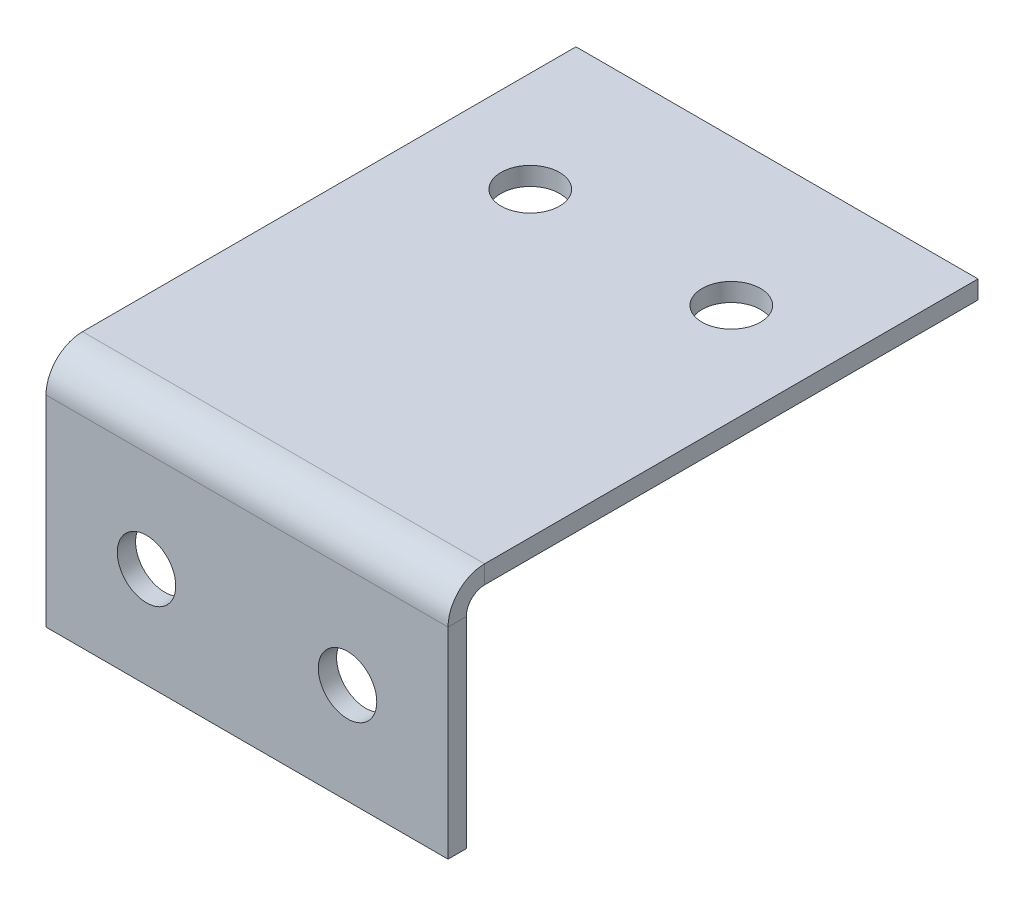
SolidWorks part; units mm, degrees
note: The reader was unsure of these and kept them because the rebuilt part matched: bend radius of "BaseBend1".
ref_plane "Front Plane" through (0, 0, 0) normal (0, 0, 1) x (1, 0, 0)
ref_plane "Top Plane" through (0, 0, 0) normal (0, 1, 0) x (1, 0, 0)
ref_plane "Right Plane" through (0, 0, 0) normal (1, 0, 0) x (0, 0, -1)
sketch "Sketch1" plane through (0, 0, 0) normal (1, 0, 0) x (0, 0, -1)
  line L0 (0, 0) -> (0, 19.05)
  line L1 (0, 19.05) -> (44.45, 19.05)
  dimension "D1" = 19.05
  dimension "D2" = 44.45
base flange "Base-Flange1" sketch "Sketch1" end condition mid plane depth 34.925 reverse direction yes thickness 1.5875 reverse thickness direction yes bend radius 1.5875
bend "BaseBend1" bend radius 1.5875 bend angle 90 parameters "D5"=1
sketch "Sketch6" plane through (0, 0, 1.5875) normal (0, 0, 1) x (1, 0, 0)
  line L0 (-17.4625, 8.7312) -> (17.4625, 8.7312) construction
  line L1 (-17.4625, 0) -> (-17.4625, 17.4625) construction
  line L2 (17.4625, 0) -> (17.4625, 17.4625) construction
  line L3 (-17.4625, 17.4625) -> (-8.7313, 8.7312) construction
  line L4 (-8.7313, 8.7312) -> (0, 17.4625) construction
  line L5 (-17.4625, 17.4625) -> (17.4625, 17.4625) construction
  line L6 (0, 17.4625) -> (8.7313, 8.7312) construction
  line L7 (8.7313, 8.7312) -> (17.4625, 17.4625) construction
  line L8 (-8.7313, 8.7312) -> (0, 0) construction
  line L9 (-17.4625, 0) -> (17.4625, 0) construction
  line L10 (0, 0) -> (8.7313, 8.7312) construction
  circle A0 centre (-8.7313, 8.7312) radius 2.54
  circle A1 centre (8.7313, 8.7312) radius 2.54
  dimension "D1" = 5.08
extrude "Cut-Extrude1" cut sketch "Sketch6" against normal blind 2.54
sketch "Sketch7" plane through (0, 20.6375, 0) normal (0, 1, 0) x (1, 0, 0)
  line L0 (-17.4625, 31.75) -> (17.4625, 31.75) construction
  line L4 (-17.4625, 1.5875) -> (-17.4625, 44.45) construction
  line L5 (17.4625, 1.5875) -> (17.4625, 44.45) construction
  line L6 (-17.4625, 44.45) -> (17.4625, 44.45) construction
  line L7 (-8.7313, 31.75) -> (0, 44.45) construction
  line L8 (0, 44.45) -> (8.7312, 31.75) construction
  line L9 (8.7312, 31.75) -> (17.4625, 44.45) construction
  circle A0 centre (-8.7313, 31.75) radius 2.54
  circle A1 centre (8.7312, 31.75) radius 2.54
  dimension "D2" = 12.7
  dimension "D1" = 5.08
extrude "Cut-Extrude2" cut sketch "Sketch7" against normal blind 2.54
sketch "Bend-Lines1" [suppressed] plane through (0, 0, 0) normal (0, 1, 0) x (1, 0, 0)
sketch "Bounding-Box1" [suppressed] plane through (0, 0, 0) normal (0, 1, 0) x (1, 0, 0)
sheet metal parameters "Sheet-Metal2" thickness 1.5875 parameters "D1"=1.5875
flat pattern "Flat-Pattern2" [suppressed]
sketch "Bend-Lines2" plane through (0, 26.9875, 0) normal (0, 1, 0) x (1, 0, 0)
  line L0 (18.2562, -0.2827) -> (-18.2562, -0.2827) construction
  line L1 (18.2562, -0.2827) -> (-18.2562, -0.2827) construction
sketch3d "Bounding-Box2" [suppressed]
  line L0 (0, -25.9655, 0) -> (0, 50.8, 0) construction
  line L1 (36.5125, -25.9655, 0) -> (36.5125, 50.8, 0) construction
  line L2 (0, -25.9655, 0) -> (36.5125, -25.9655, 0) construction
  line L3 (0, 50.8, 0) -> (36.5125, 50.8, 0) construction
bend of the flat pattern "Flatten-<BaseBend1>1"
sheet metal parameters "Sheet-Metal3" thickness 1.5875 parameters "D1"=1.5875
flat pattern "Flat-Pattern2"
sketch "Bend-Lines2" plane through (0, 26.9875, 0) normal (0, 1, 0) x (1, 0, 0)
  line L0 (18.2562, -0.2827) -> (-18.2563, -0.2827) construction
  line L1 (18.2562, -0.2827) -> (-18.2563, -0.2827) construction
sketch3d "Bounding-Box2" [suppressed]
  line L0 (0, -25.9655, 0) -> (0, 50.8, 0) construction
  line L1 (36.5125, -25.9655, 0) -> (36.5125, 50.8, 0) construction
  line L2 (0, -25.9655, 0) -> (36.5125, -25.9655, 0) construction
  line L3 (0, 50.8, 0) -> (36.5125, 50.8, 0) construction
bend of the flat pattern "Flatten-<BaseBend1>1"
sheet metal parameters "Sheet-Metal4" thickness 1.5875 parameters "D1"=1.5875
flat pattern "Flat-Pattern2"
sketch "Bend-Lines2" plane through (0, 20.6375, 0) normal (0, 1, 0) x (1, 0, 0)
  line L0 (17.4625, -0.2827) -> (-17.4625, -0.2827) construction
  line L1 (17.4625, -0.2827) -> (-17.4625, -0.2827) construction
sketch3d "Bounding-Box2" [suppressed]
  line L0 (0, -19.6155, 0) -> (0, 44.45, 0) construction
  line L1 (34.925, -19.6155, 0) -> (34.925, 44.45, 0) construction
  line L2 (0, -19.6155, 0) -> (34.925, -19.6155, 0) construction
  line L3 (0, 44.45, 0) -> (34.925, 44.45, 0) construction
bend of the flat pattern "Flatten-<BaseBend1>1"
